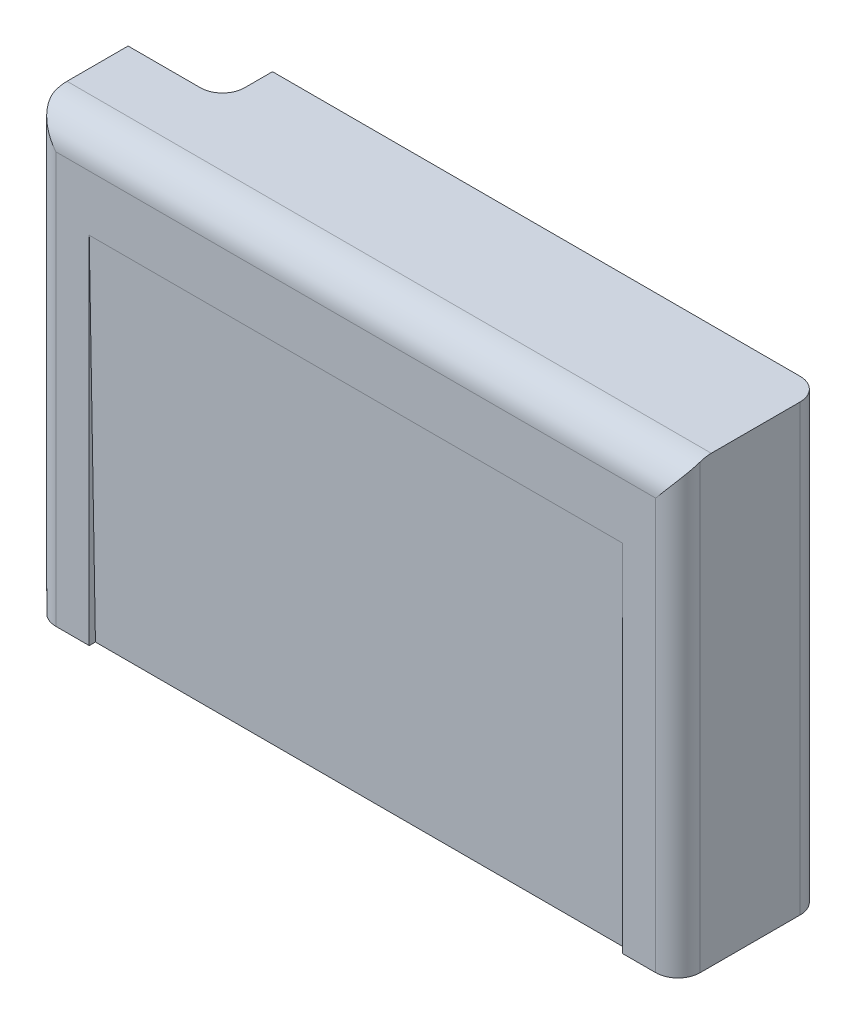
SolidWorks part; units mm, degrees
material "K110"
ref_plane "Front Plane" through (0, 0, 0) normal (0, 0, 1) x (1, 0, 0)
ref_plane "Top Plane" through (0, 0, 0) normal (0, 1, 0) x (1, 0, 0)
ref_plane "Right Plane" through (0, 0, 0) normal (1, 0, 0) x (0, 0, -1)
sketch "Sketch1" plane through (0, 0, 0) normal (0, 1, 0) x (1, 0, 0)
  line L1 (-29, -6.5) -> (29, -6.5)
  line L2 (-29, -6.5) -> (-29, 6.5)
  line L3 (-29, 6.5) -> (29, 6.5)
  line L4 (29, -6.5) -> (29, 6.5)
  line L5 (-29, -6.5) -> (29, 6.5) construction
  line L6 (-29, 6.5) -> (29, -6.5) construction
  point P0 (0, 0)
  dimension "D1" = 13
  dimension "D2" = 58
extrude "Boss-Extrude1" add sketch "Sketch1" against normal blind 40
fillet "Fillet1" radius 2 4 edges at (-29, -20, -6.5) (-29, -20, 6.5) (29, -20, -6.5) (29, -20, 6.5)
fillet "Fillet2" radius 3 1 edges at (0, 0, 6.5) tangent propagation no
hole_wizard "M6 Tapped Hole1" positions "Sketch6" profile "Sketch3" tap size "M6" standard "ISO"
sketch "Sketch6" plane through (0, -40, 0) normal (0, -1, 0) x (-1, 0, 0)
  line L0 (-29, -4.5) -> (-29, 4.5) construction
  line L1 (29, 4.5) -> (29, -4.5) construction
  point P0 (-21.5, 0)
  point P2 (14, 0)
  dimension "D1" = 7.5
  dimension "D2" = 15
sketch "Sketch3" plane through (21.5, -40, 0) normal (1, 0, 0) x (0, 0, -1)
  line L0 (0, 0) -> (0, 18.5022)
  line L1 (0, 18.5022) -> (2.5, 17)
  line L2 (2.5, 17) -> (2.5, 0.525)
  line L3 (2.5, 0.525) -> (3.025, 0)
  line L5 (3.025, 0) -> (0, 0)
  line L6 (-2.5, 0.525) -> (-3.025, 0) construction
  line L10 (0, 18.5022) -> (-2.5, 17) construction
  line L11 (0, -6.35) -> (0, 107.95) construction
  dimension "Tap Drill Dia." = 5
  dimension "Tap Drill Depth" = 17
  dimension "Near C'Sink Dia." = 6.05
  dimension "Near C'Sink Angle" = 90
  dimension "Drill Angle" = 118
cosmetic thread "Hole Thread1" parameters "D1"=12, "D2"=6
cosmetic thread "Hole Thread2" parameters "D1"=12, "D2"=6
sketch "Sketch5" plane through (0, 0, 0) normal (1, 0, 0) x (0, 0, -1)
  line L4 (-6.5, -8) -> (-5.9414, -40)
  line L5 (-6.5, -40) -> (-6.5, -3) construction
  line L6 (-6.5, -40) -> (-4.5, -40) construction
  line L7 (-5.9414, -40) -> (-6.5, -40)
  line L8 (-6.5, -40) -> (-6.5, -8)
  dimension "D1" = 5
  dimension "D2" = 1
extrude "Cut-Extrude1" cut sketch "Sketch5" against normal mid plane 48
sketch "Sketch7" plane through (0, 0, 0) normal (0, 1, 0) x (1, 0, 0)
  line L0 (27, 6.5) -> (-27, 6.5) construction
  line L1 (-29, 4.5) -> (-29, -3.5) construction
  line L2 (-20.5, 6.5) -> (-27, 6.5)
  line L3 (-29, 4.5) -> (-29, 2)
  line L4 (-29, 2) -> (-20.5, 2)
  line L5 (-20.5, 2) -> (-20.5, 6.5)
  line L6 (-29, -3.5) -> (29, -3.5) construction
  arc A0 (-27, 6.5) -> (-29, 4.5) centre (-27, 4.5) ccw construction
  arc A1 (-27, 6.5) -> (-29, 4.5) centre (-27, 4.5) ccw
  dimension "D1" = 5.5
  dimension "D2" = 8.5
extrude "Cut-Extrude2" cut sketch "Sketch7" against normal up to next
fillet "Fillet3" radius 2 1 edges at (-20.5, -20, -2)
